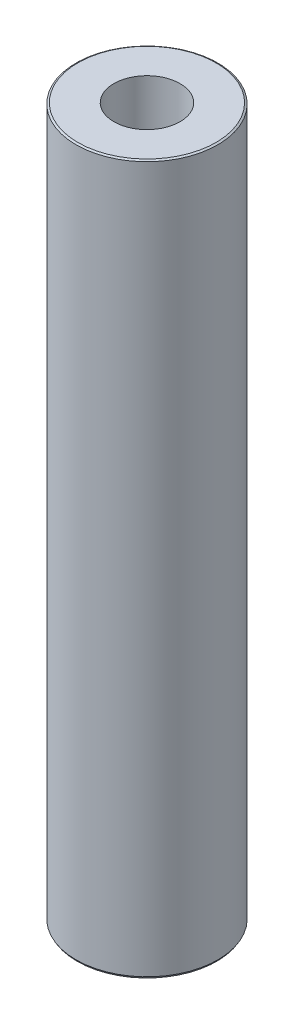
SolidWorks part; units mm, degrees
ref_plane "Front Plane" through (0, 0, 0) normal (0, 0, 1) x (1, 0, 0)
ref_plane "Top Plane" through (0, 0, 0) normal (0, 1, 0) x (1, 0, 0)
ref_plane "Right Plane" through (0, 0, 0) normal (1, 0, 0) x (0, 0, -1)
sketch "Sketch1" plane through (0, 0, 0) normal (0, 1, 0) x (1, 0, 0)
  circle A0 centre (0, 0) radius 60
  dimension "SHAFT_OD" = 120
extrude "Boss-Extrude1" add sketch "Sketch1" along normal blind 600
sketch "Sketch2" plane through (0, 0, 0) normal (0, 1, 0) x (1, 0, 0)
  circle A0 centre (0, 0) radius 28.003
  dimension "BORE_D" = 56.006
extrude "Cut-Extrude1" cut sketch "Sketch2" along normal through all
chamfer "Chamfer1" distance 0.8879 angle 60 2 edges at (0, 600, 60) (0, 0, 60) first distance on face at (0, 600, 60) first distance on face at (0, 0, 28.003)
